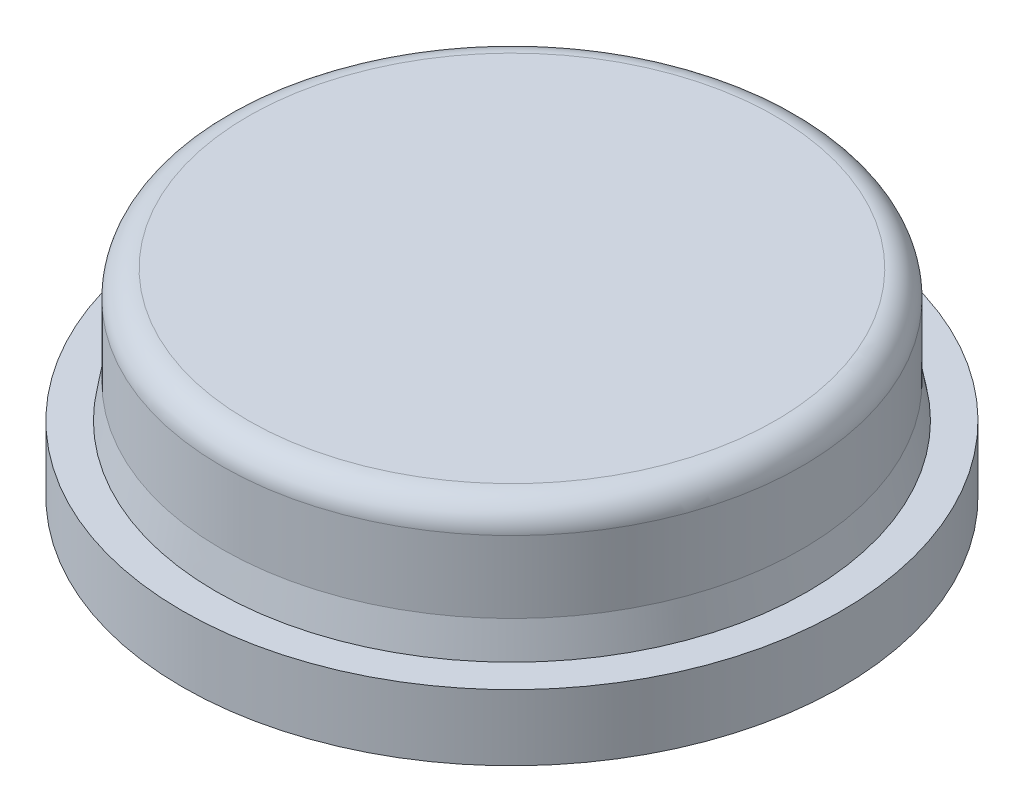
SolidWorks part; units mm, degrees
ref_plane "前视基准面" through (0, 0, 0) normal (0, 0, 1) x (1, 0, 0)
ref_plane "上视基准面" through (0, 0, 0) normal (0, 1, 0) x (1, 0, 0)
ref_plane "右视基准面" through (0, 0, 0) normal (1, 0, 0) x (0, 0, -1)
sketch "草图1" plane through (0, 0, 0) normal (0, 1, 0) x (1, 0, 0)
  circle A0 centre (0, 0) radius 4.5
  dimension "D1" = 9
sketch "草图2" plane through (0, 0, 0) normal (0, 1, 0) x (1, 0, 0)
  circle A2 centre (0, 0) radius 5
  circle A3 centre (0, 0) radius 5
  dimension "D1" = 0.5
extrude "凸台-拉伸1" add sketch "草图2" along normal blind 1
sketch "草图3" plane through (0, 1, 0) normal (0, 1, 0) x (1, 0, 0)
  circle A2 centre (0, 0) radius 4.4
  circle A3 centre (0, 0) radius 4.4
  dimension "D1" = 0.1
extrude "凸台-拉伸2" add sketch "草图3" along normal blind 2
fillet "圆角1" radius 0.4 1 edges at (0, 3, 4.4)
chamfer "倒角1" distance 0.09 angle 80 1 edges at (0, 1, 4.4) first distance on face at (0, 1, 4.4)
ref_axis "中心轴" through (0, 3.7378, 0) along (0, -1, 0)
sketch "草图4" plane through (0, 0, 0) normal (0, -1, 0) x (1, 0, 0)
  circle A0 centre (0, 0) radius 1.65
  dimension "D1" = 3.3
extrude "切除-拉伸1" cut sketch "草图4" against normal offset from surface (1.65 mm away) 1.35 up to face at (0, 3, 4)
